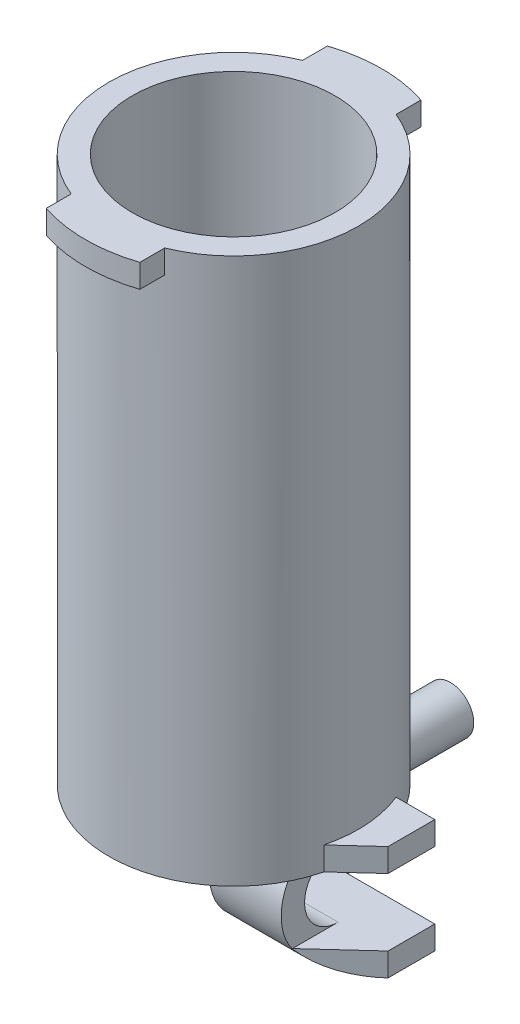
SolidWorks part; units mm, degrees
ref_plane "Front Plane" through (0, 0, 0) normal (0, 0, 1) x (1, 0, 0)
ref_plane "Top Plane" through (0, 0, 0) normal (0, 1, 0) x (1, 0, 0)
ref_plane "Right Plane" through (0, 0, 0) normal (1, 0, 0) x (0, 0, -1)
sketch "Sketch1" plane through (0, 0, 0) normal (0, 1, 0) x (1, 0, 0)
  circle A0 centre (0, 0) radius 8
extrude "Boss-Extrude1" add sketch "Sketch1" along normal blind 35
shell "Shell1" thickness 1.5 removed face at (0, 35, 8)
sketch "Sketch2" plane through (0, 0, 0) normal (0, -1, 0) x (1, 0, 0)
  circle A2 centre (0, -3) radius 3.5
extrude "Boss-Extrude2" add sketch "Sketch2" along normal blind 5.3
sketch "Sketch3" plane through (0, 0, 0) normal (1, 0, 0) x (0, 0, -1)
  line L0 (0, 4.9697) -> (0, 0) construction
  line L1 (0, 1.5) -> (0, 0)
  line L2 (0, -4.3) -> (0, -5.8)
  line L3 (0, -4.3) -> (0, -6.6365) construction
  arc A0 (0, 0) -> (0, -4.3) centre (0, -2.15) ccw
  arc A1 (0, 1.5) -> (0, -5.8) centre (0, -2.15) ccw
extrude "Boss-Extrude3" add sketch "Sketch3" along normal blind 6.7 contours A1 L2 A0 L1
sketch "Sketch4" plane through (0, -5.3, 0) normal (0, -1, 0) x (1, 0, 0)
  line L0 (0, 0) -> (2.1, 0)
  line L1 (6.7, 0) -> (0, 0) construction
  line L2 (2.1, 0) -> (2.1, 5.477)
  line L3 (2.1, 5.477) -> (0, 5.477)
  line L4 (0, 5.477) -> (0, 0)
extrude "Cut-Extrude1" cut sketch "Sketch4" along normal blind 9
sketch "Sketch5" plane through (0, 0, 0) normal (0, -1, 0) x (1, 0, 0)
  line L0 (0, 0.5) -> (0, 3.65)
  line L1 (0, 3.65) -> (0, 1.8439) construction
  line L2 (2.1, -0.2) -> (2.1, 3.65)
  line L3 (6.7, 3.65) -> (0, 3.65) construction
  line L4 (2.1, 3.65) -> (0, 3.65)
  arc A0 (2.1, -0.2) -> (0, 0.5) centre (0, -3) ccw
extrude "Cut-Extrude2" cut sketch "Sketch5" along normal blind 9
sketch "Sketch6" plane through (0, -5.3, 0) normal (0, -1, 0) x (1, 0, 0)
  line L0 (-1.4347, -3) -> (2.2984, -3) construction
ref_plane "Plane1" through (0, 0, -3) normal (0, 0, 1) x (1, 0, 0)
sketch "Sketch8" plane through (0, 0, -3) normal (0, 0, 1) x (1, 0, 0)
  line L0 (0, 0) -> (0, -7.6173) construction
  circle A1 centre (0, -2.7845) radius 2.45
extrude "Boss-Extrude4" add sketch "Sketch8" against normal blind 4.8
sketch "Sketch9" plane through (0, 0, -7.8) normal (0, 0, -1) x (-1, 0, 0)
  circle A0 centre (0, -2.7845) radius 1.5
extrude "Boss-Extrude5" add sketch "Sketch9" along normal blind 6.1
sketch "Sketch10" plane through (0, 0, -13.9) normal (0, 0, -1) x (-1, 0, 0)
  circle A0 centre (0, -2.7845) radius 0.75
extrude "Cut-Extrude3" cut sketch "Sketch10" against normal blind 10.1
sketch "Sketch11" plane through (0, -5.3, 0) normal (0, -1, 0) x (1, 0, 0)
  circle A1 centre (0, -3) radius 2
extrude "Cut-Extrude4" cut sketch "Sketch11" against normal through all
sketch "Sketch12" plane through (0, -5.3, 0) normal (0, -1, 0) x (1, 0, 0)
  circle A0 centre (0, -3) radius 2
extrude "Boss-Extrude6" add sketch "Sketch12" against normal blind 1.5 separate body
sketch "Sketch16" plane through (6.7, 0, 0) normal (1, 0, 0) x (0, 0, -1)
  line L0 (0, -4.3) -> (0, -5.8)
  line L1 (0, -4.3) -> (3, -4.3)
  line L2 (0, -5.8) -> (3, -5.8)
  line L3 (3, -4.3) -> (3, -5.8)
  line L4 (0, -4.3) -> (0, -5.8) construction
  line L5 (-2.15, -2.15) -> (-4.1057, -2.15) construction
  line L6 (0, 1.5) -> (3, 1.5)
  line L7 (3, 0) -> (3, 1.5)
  line L8 (0, 0) -> (3, 0)
  line L9 (0, 0) -> (0, 1.5)
  arc A0 (0, 0) -> (0, -4.3) centre (0, -2.15) ccw construction
extrude "Boss-Extrude9" add sketch "Sketch16" along normal blind 3.2 and the other way up to surface (4.6 mm away) other way up to face at (2.1, -2.7511, 1.7196)
sketch "Sketch17" plane through (0, -4.3, 0) normal (0, 1, 0) x (1, 0, 0)
  line L0 (6.7, 0) -> (6.7, -2.9284)
  line L5 (6.7, -2.9284) -> (9.9, 0)
  line L6 (9.9, 3) -> (9.9, 0) construction
  line L7 (9.9, 0) -> (6.7, 0)
extrude "Boss-Extrude10" add sketch "Sketch17" against normal up to surface (1.5 mm away) contours L0 L5 L7 up to face at (6.14, -5.8, -1.2)
sketch "Sketch18" plane through (6.7, 0, 0) normal (-1, 0, 0) x (0, 0, 1)
  line L0 (2.9284, -5.8) -> (2.9284, -4.3288)
  line L1 (2.9284, -5.8) -> (0, -5.8)
  arc A0 (0, -5.8) -> (2.9284, -4.3288) centre (0, -2.15) ccw
extrude "Cut-Extrude5" cut sketch "Sketch18" against normal through all
sketch "Sketch19" plane through (0, -4.3, 0) normal (0, 1, 0) x (1, 0, 0)
  line L0 (9.9, 0) -> (6.7, -2.9284)
  line L5 (6.7, 0) -> (6.7, -2.9284)
  line L6 (9.9, 0) -> (6.7, 0)
extrude "Boss-Extrude11" add sketch "Sketch19" along normal up to surface (5.8 mm away) contours L0 L5 L6 up to face at (8.8402, 1.5, -1.507)
sketch "Sketch20" plane through (0, 0, 0) normal (0, 0, -1) x (-1, 0, 0)
  line L0 (-3.5, -4.3) -> (-9.9, -4.3) construction
  line L1 (-9.9, 0) -> (-6.7, 0)
  line L2 (-9.9, 0) -> (-9.9, -4.3)
  line L3 (-9.9, -4.3) -> (-6.7, -4.3)
  line L4 (-6.7, 0) -> (-6.7, -4.3)
extrude "Cut-Extrude6" cut sketch "Sketch20" against normal through all
sketch "Sketch21" plane through (2.1, 0, 0) normal (-1, 0, 0) x (0, 0, 1)
  circle A0 centre (0, -2.15) radius 2.15
extrude "Boss-Extrude12" add sketch "Sketch21" against normal blind 0.001
mirror "Mirror1" about plane through (0, 0, 0) normal (1, 0, 0) of bodies 119
sketch "Sketch22" plane through (0, 35, 0) normal (0, 1, 0) x (1, 0, 0)
  line L2 (3, 7.4162) -> (3, 9.0139)
  line L4 (-3, 7.4162) -> (-3, 9.0139)
  line L5 (3, -7.4162) -> (3, -9.0139)
  line L6 (-3, -7.4162) -> (-3, -9.0139)
  arc A0 (3, 9.0139) -> (-3, 9.0139) centre (0, 0) ccw
  arc A1 (3, 7.4162) -> (-3, 7.4162) centre (0, 0) ccw
  arc A2 (3, -7.4162) -> (-3, -7.4162) centre (0, 0) cw
  arc A3 (3, -9.0139) -> (-3, -9.0139) centre (0, 0) cw
extrude "Boss-Extrude13" add sketch "Sketch22" against normal blind 1.5
